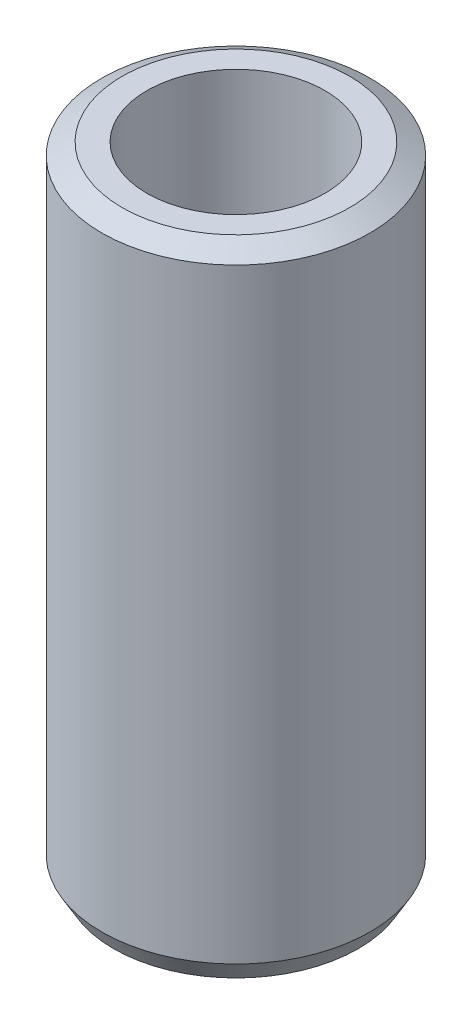
SolidWorks part; units mm, degrees
ref_plane "Front Plane" through (0, 0, 0) normal (0, 0, 1) x (1, 0, 0)
ref_plane "Top Plane" through (0, 0, 0) normal (0, 1, 0) x (1, 0, 0)
ref_plane "Right Plane" through (0, 0, 0) normal (1, 0, 0) x (0, 0, -1)
sketch "Sketch1" plane through (0, 0, 0) normal (0, 1, 0) x (1, 0, 0)
  circle A0 centre (0, 0) radius 27.5
  dimension "SHAFT_OD" = 55
extrude "Boss-Extrude1" add sketch "Sketch1" along normal blind 130.6711
sketch "Sketch2" plane through (0, 0, 0) normal (0, 1, 0) x (1, 0, 0)
  circle A0 centre (0, 0) radius 18.2519
  dimension "BORE_D" = 36.5038
extrude "Cut-Extrude1" cut sketch "Sketch2" along normal through all
chamfer "Chamfer1" distance 2.4132 angle 60 2 edges at (0, 130.6711, 27.5) (0, 0, 27.5) first distance on face at (0, 130.6711, 27.5) first distance on face at (0, 0, 18.2519)
